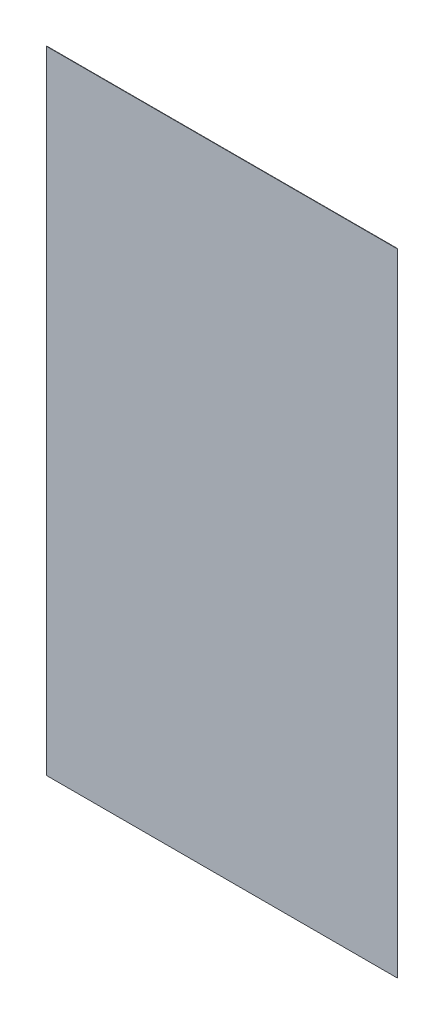
SolidWorks part; units mm, degrees
ref_plane "Front Plane" through (0, 0, 0) normal (0, 0, 1) x (1, 0, 0)
ref_plane "Top Plane" through (0, 0, 0) normal (0, 1, 0) x (1, 0, 0)
ref_plane "Right Plane" through (0, 0, 0) normal (1, 0, 0) x (0, 0, -1)
sketch "Sketch1" plane through (0, 0, 0) normal (0, 0, 1) x (1, 0, 0)
  line L1 (0, 0) -> (903, 0)
  line L2 (0, 0) -> (0, 1625)
  line L3 (0, 1625) -> (903, 1625)
  line L4 (903, 0) -> (903, 1625)
  dimension "D1" = 903
  dimension "D2" = 1625
extrude "Boss-Extrude1" add sketch "Sketch1" along normal blind 1
